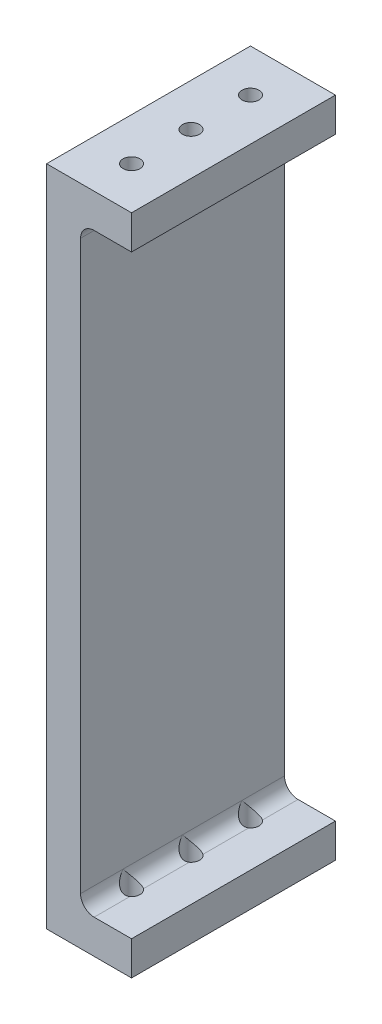
SolidWorks part; units mm, degrees
ref_plane "Front Plane" through (0, 0, 0) normal (0, 0, 1) x (1, 0, 0)
ref_plane "Top Plane" through (0, 0, 0) normal (0, 1, 0) x (1, 0, 0)
ref_plane "Right Plane" through (0, 0, 0) normal (1, 0, 0) x (0, 0, -1)
sketch "Sketch1" plane through (0, 0, 0) normal (0, 0, 1) x (1, 0, 0)
  line L0 (7.9375, -55.5625) -> (7.9375, 55.5625) construction
  line L1 (-7.9375, -61.9125) -> (7.9375, -61.9125)
  line L2 (-7.9375, -61.9125) -> (-7.9375, 61.9125)
  line L3 (-7.9375, 61.9125) -> (7.9375, 61.9125)
  line L4 (7.9375, -61.9125) -> (7.9375, -55.5625)
  line L5 (-7.9375, -61.9125) -> (7.9375, 61.9125) construction
  line L6 (-7.9375, 61.9125) -> (7.9375, -61.9125) construction
  line L7 (7.9375, 55.5625) -> (-1.5875, 55.5625)
  line L8 (7.9375, 55.5625) -> (7.9375, -55.5625) construction
  line L9 (7.9375, -55.5625) -> (-1.5875, -55.5625)
  line L10 (-1.5875, 55.5625) -> (-1.5875, -55.5625)
  line L11 (7.9375, 55.5625) -> (7.9375, 61.9125)
  point P0 (0, 0)
  point P10 (-21.2875, 69.85)
  dimension "D1" = 6.35
  dimension "D2" = 6.35
  dimension "4.1" = 123.825
  dimension "D4" = 15.875
extrude "Boss-Extrude1" add sketch "Sketch1" along normal blind 38.1
sketch "Sketch2" plane through (0, 61.9125, 0) normal (0, 1, 0) x (1, 0, 0)
  line L0 (-7.9375, 0) -> (0, -7.9375) construction
  line L1 (0, -7.9375) -> (7.9375, 0) construction
  line L2 (7.9375, 0) -> (7.9375, -38.1) construction
  line L3 (7.9375, -38.1) -> (7.9375, 0) construction
  line L4 (7.9375, -38.1) -> (0, -30.1625) construction
  line L5 (0, -30.1625) -> (0, -19.05) construction
  line L6 (0, -19.05) -> (0, -7.9375) construction
  circle A0 centre (0, -7.9375) radius 1.5875
  circle A1 centre (0, -19.05) radius 1.5875
  circle A2 centre (0, -30.1625) radius 1.5875
  point P10 (0, -29.0348)
  point P14 (0, 0)
  dimension "D1" = 3.175
extrude "Cut-Extrude1" cut sketch "Sketch2" against normal through all
fillet "Fillet2" radius 2.54 8 edges at (-1.5875, -55.5625, 34.1313) (-1.5875, -55.5625, 3.9688) (-1.5875, -55.5625, 24.6063) (-1.5875, -55.5625, 13.4938) (-1.5875, 55.5625, 34.1313) (-1.5875, 55.5625, 3.9688) (-1.5875, 55.5625, 13.4938) (-1.5875, 55.5625, 24.6063)
equation "\"height\"= 4.875"
equation "\"4.1@Sketch1\"=\"height\""
